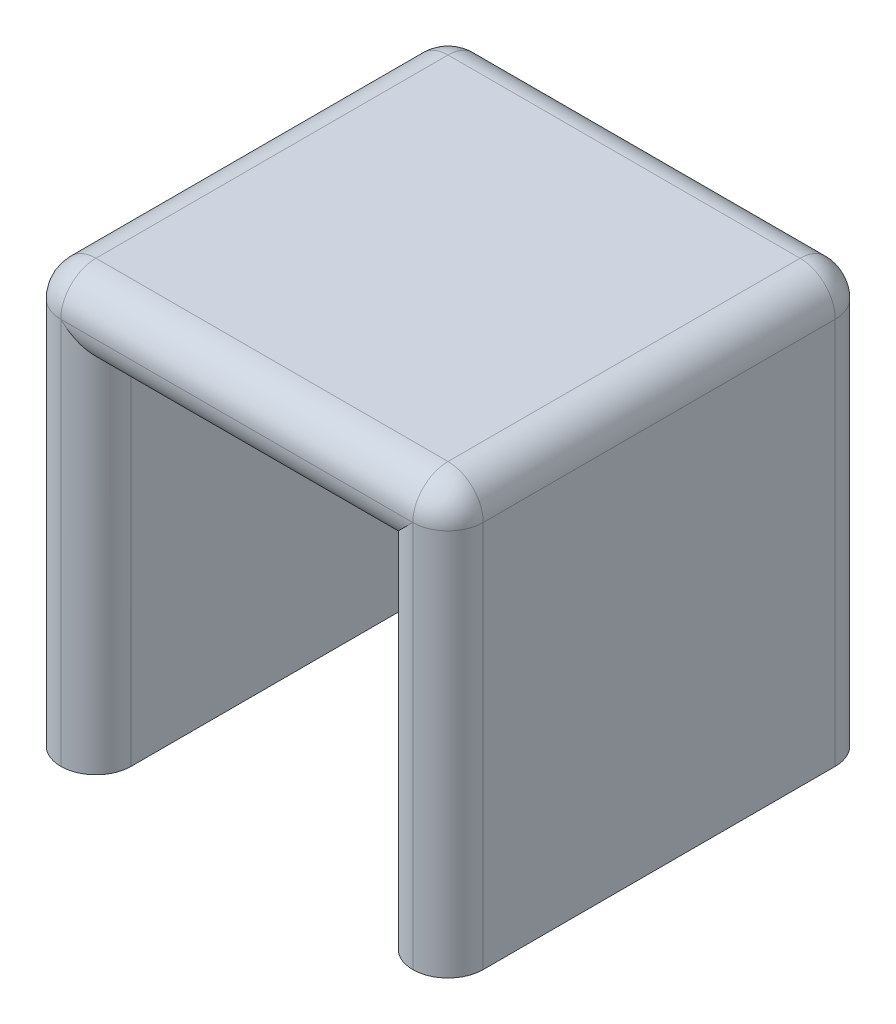
SolidWorks part; units mm, degrees
ref_plane "Front Plane" through (0, 0, 0) normal (0, 0, 1) x (1, 0, 0)
ref_plane "Top Plane" through (0, 0, 0) normal (0, 1, 0) x (1, 0, 0)
ref_plane "Right Plane" through (0, 0, 0) normal (1, 0, 0) x (0, 0, -1)
sketch "Sketch1" plane through (0, 0, 0) normal (0, 0, 1) x (1, 0, 0)
  line L0 (0, 0) -> (0, 12)
  line L1 (0, 12) -> (12, 12)
  line L2 (12, 12) -> (12, 0)
  line L3 (12, 0) -> (10, 0)
  line L4 (10, 0) -> (10, 10)
  line L5 (10, 10) -> (2, 10)
  line L6 (2, 10) -> (2, 0)
  line L7 (2, 0) -> (0, 0)
  dimension "D1" = 12
  dimension "D2" = 12
  dimension "D3" = 12
  dimension "D4" = 10
  dimension "D5" = 10
  dimension "D6" = 8
  dimension "D7" = 2
extrude "Boss-Extrude1" add sketch "Sketch1" along normal blind 12
fillet "Fillet3" radius 1 14 edges at (2, 5, 12) (0, 6, 12) (12, 6, 12) (10, 5, 12) (6, 10, 12) (6, 12, 12) (0, 12, 6) (12, 12, 6) (12, 6, 0) (6, 12, 0) (0, 6, 0) (10, 5, 0) (6, 10, 0) (2, 5, 0)
